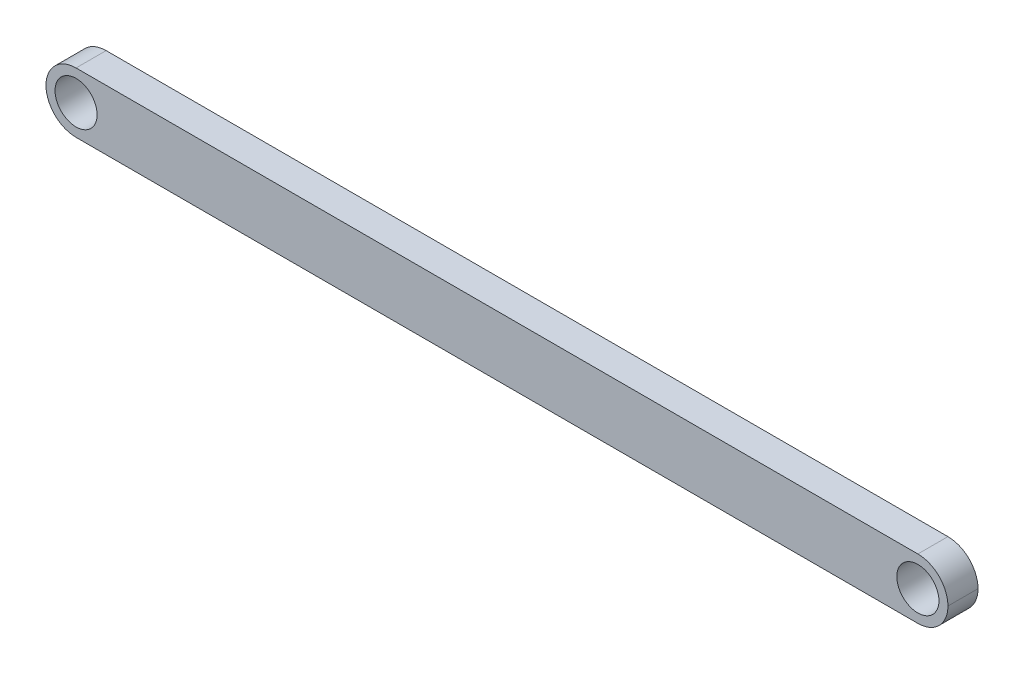
SolidWorks part; units mm, degrees
material "Gray Cast Iron"
ref_plane "前视基准面" through (0, 0, 0) normal (0, 0, 1) x (1, 0, 0)
ref_plane "上视基准面" through (0, 0, 0) normal (0, 1, 0) x (1, 0, 0)
ref_plane "右视基准面" through (0, 0, 0) normal (1, 0, 0) x (0, 0, -1)
other "Configuration Table"
sketch "草图1" plane through (0, 0, 0) normal (0, 0, 1) x (1, 0, 0)
  line L1 (-150, -10) -> (150, -10)
  line L2 (-150, -10) -> (-150, 10)
  line L3 (-150, 10) -> (150, 10)
  line L4 (150, -10) -> (150, 10)
  line L5 (-150, -10) -> (150, 10) construction
  line L6 (-150, 10) -> (150, -10) construction
  circle A0 centre (-140, 0) radius 7
  circle A1 centre (140, 0) radius 7
  point P0 (0, 0)
  dimension "D3" = 14
  dimension "D4" = 14
  dimension "D1" = 20
  dimension "D2" = 300
  dimension "D5" = 140
  dimension "D6" = 140
extrude "凸台-拉伸1" add sketch "草图1" along normal blind 10
fillet "圆角1" radius 10 4 edges at (150, 10, 5) (150, -10, 5) (-150, -10, 5) (-150, 10, 5)
